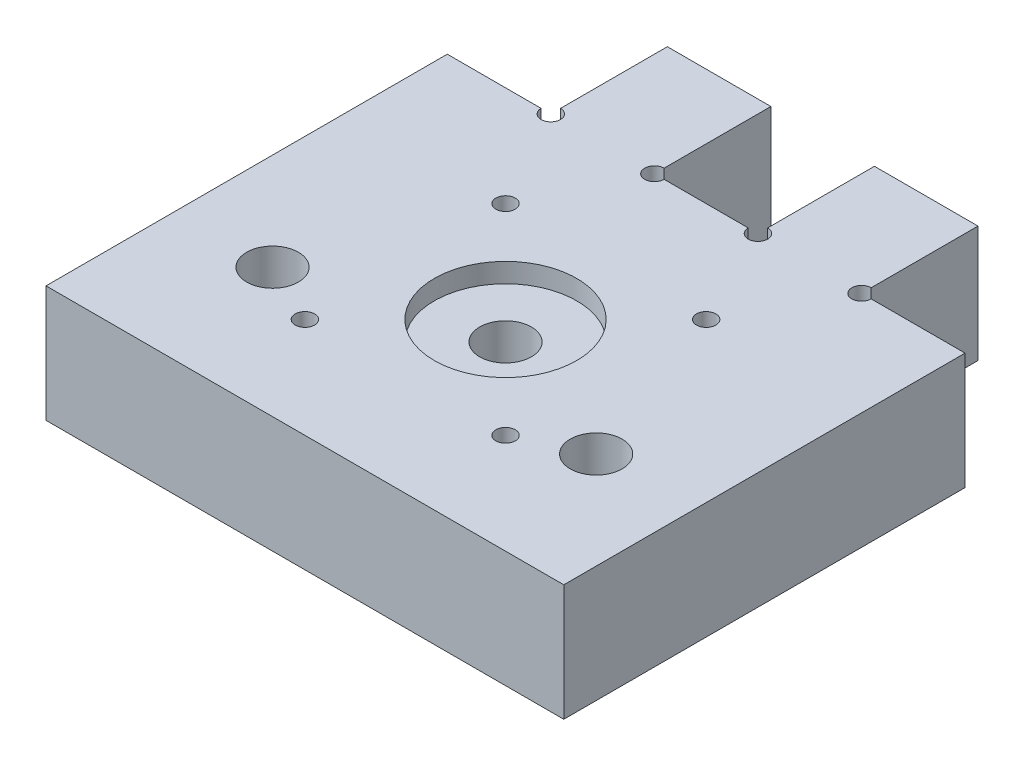
SolidWorks part; units mm, degrees
ref_plane "Front Plane" through (0, 0, 0) normal (0, 0, 1) x (1, 0, 0)
ref_plane "Top Plane" through (0, 0, 0) normal (0, 1, 0) x (1, 0, 0)
ref_plane "Right Plane" through (0, 0, 0) normal (1, 0, 0) x (0, 0, -1)
sketch "Sketch1" plane through (0, 0, 0) normal (0, 1, 0) x (1, 0, 0)
  line L0 (-1000, 0) -> (49000, 0) construction
  line L5 (0, -1000) -> (0, 49000) construction
  line L6 (-40, 31) -> (-24, 31)
  line L7 (-40, -31) -> (40, -31)
  line L8 (-40, -31) -> (-40, 31)
  line L9 (-24, 49) -> (-8, 49)
  line L10 (40, -31) -> (40, 31)
  line L11 (-24, 49) -> (-24, 31)
  line L12 (-8, 49) -> (-8, 31)
  line L13 (8, 49) -> (8, 31)
  line L14 (24, 49) -> (24, 31)
  line L16 (24, 31) -> (40, 31)
  line L17 (8, 49) -> (24, 49)
  line L18 (-8, 31) -> (8, 31)
  circle A10 centre (0, 0) radius 4
  circle A11 centre (15.5, 15.5) radius 1.5
  circle A12 centre (-15.5, 15.5) radius 1.5
  circle A13 centre (-15.5, -15.5) radius 1.5
  circle A14 centre (15.5, -15.5) radius 1.5
  circle A16 centre (-25, -11) radius 4
  circle A17 centre (25, -11) radius 4
  point P6 (0, 31)
  point P10 (-40, 0)
  point P32 (0, 0)
  point P33 (0, 0)
  dimension "D3" = 8
  dimension "D4" = 15.5
  dimension "D6" = 3
  dimension "D12" = 25
  dimension "D2" = 80
  dimension "D5" = 15.5
  dimension "D7" = 18
  dimension "D9" = 4
  dimension "D8" = 16
  dimension "D10" = 16
  dimension "D11" = 80
  dimension "D14" = 20
extrude "Boss-Extrude1" add sketch "Sketch1" along normal blind 18
sketch "Sketch2" plane through (0, 18, 0) normal (0, 1, 0) x (1, 0, 0)
  circle A0 centre (0, 0) radius 11
  dimension "D1" = 22
extrude "Cut-Extrude1" cut sketch "Sketch2" against normal blind 3
sketch "Sketch3" plane through (0, 18, 0) normal (0, 1, 0) x (1, 0, 0)
  circle A0 centre (-24, 31) radius 1.5
  circle A1 centre (-8, 31) radius 1.5
  circle A2 centre (8, 31) radius 1.5
  circle A3 centre (24, 31) radius 1.5
  dimension "D1" = 3
  dimension "D3" = 16
  dimension "D2" = 4
extrude "Cut-Extrude2" cut sketch "Sketch3" against normal through all
